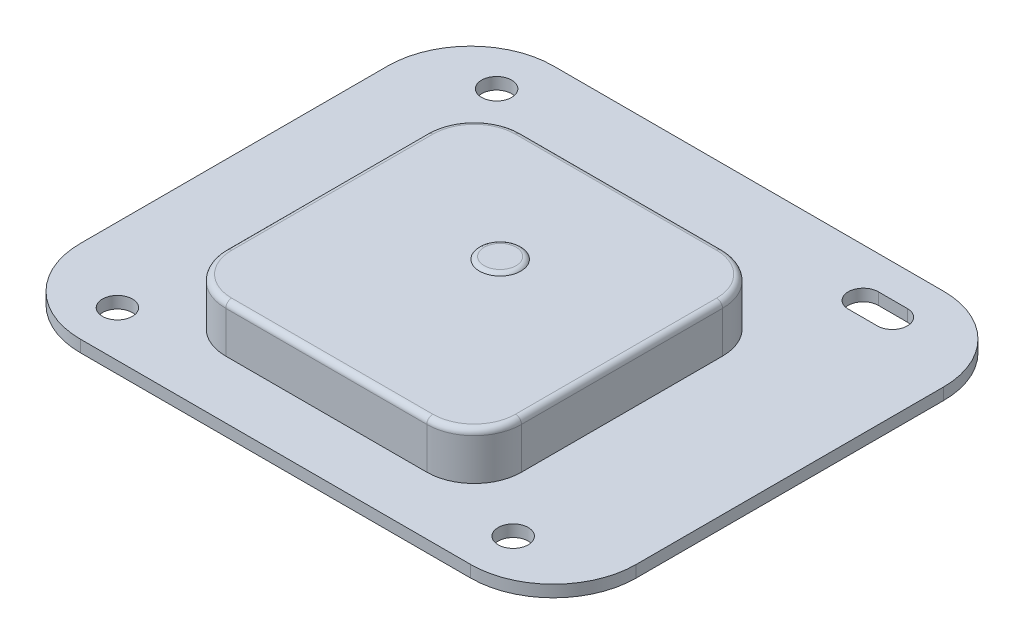
SolidWorks part; units mm, degrees
ref_plane "Front Plane" through (0, 0, 0) normal (0, 0, 1) x (1, 0, 0)
ref_plane "Top Plane" through (0, 0, 0) normal (0, 1, 0) x (1, 0, 0)
ref_plane "Right Plane" through (0, 0, 0) normal (1, 0, 0) x (0, 0, -1)
sketch "Sketch3" plane through (0, 0, 0) normal (0, 1, 0) x (1, 0, 0)
  line L0 (23.5, 20) -> (23.5, -20) construction
  line L1 (-23.5, -20) -> (23.5, -20) construction
  line L2 (-23.5, 20) -> (-23.5, -20) construction
  line L3 (-23.5, 20) -> (23.5, 20) construction
  line L4 (23.5, 20) -> (23.5, -20)
  line L5 (-23.5, -20) -> (23.5, -20)
  line L6 (-23.5, 20) -> (-23.5, -20)
  line L7 (-23.5, 20) -> (23.5, 20)
  line L8 (5.2, -11.1) -> (16.8, -11.1) construction
  line L9 (16.8, 3.9) -> (16.8, -11.1) construction
  line L10 (5.2, 3.9) -> (16.8, 3.9) construction
  line L11 (5.2, 3.9) -> (5.2, -11.1) construction
  line L12 (-20.5, 10) -> (-14.9, 10) construction
  line L13 (-20.5, 10) -> (-20.5, -0.9) construction
  line L14 (-20.5, -0.9) -> (-14.9, -0.9) construction
  line L15 (-14.9, 10) -> (-14.9, -0.9) construction
  line L16 (5.2, -11.1) -> (16.8, -11.1)
  line L17 (16.8, 3.9) -> (16.8, -11.1)
  line L18 (5.2, 3.9) -> (16.8, 3.9)
  line L19 (5.2, 3.9) -> (5.2, -11.1)
  line L20 (-20.5, 10) -> (-14.9, 10)
  line L21 (-20.5, 10) -> (-20.5, -0.9)
  line L22 (-20.5, -0.9) -> (-14.9, -0.9)
  line L23 (-14.9, 10) -> (-14.9, -0.9)
  circle A0 centre (-17.23, 15.93) radius 1.27 construction
  circle A1 centre (16.23, 15.93) radius 1.27 construction
  circle A2 centre (-17.23, -16.13) radius 1.27 construction
  circle A3 centre (16.23, -16.13) radius 1.27 construction
  circle A4 centre (-17.23, 15.93) radius 1.27
  circle A5 centre (16.23, 15.93) radius 1.27
  circle A6 centre (-17.23, -16.13) radius 1.27
  circle A7 centre (16.23, -16.13) radius 1.27
sketch "Sketch4" plane through (0, 0, 0) normal (0, 1, 0) x (1, 0, 0)
  line L0 (13.77, 14.66) -> (16.23, 14.66)
  line L1 (13.77, 17.2) -> (16.23, 17.2)
  line L4 (23.5, -20) -> (23.5, 20)
  line L5 (-23.5, -20) -> (23.5, -20)
  line L6 (-23.5, 20) -> (-23.5, -20)
  line L7 (23.5, 20) -> (-23.5, 20)
  line L8 (23.5, -20) -> (23.5, 20)
  line L9 (-23.5, -20) -> (23.5, -20)
  line L10 (-23.5, 20) -> (-23.5, -20)
  line L11 (23.5, 20) -> (-23.5, 20)
  arc A0 (13.77, 17.2) -> (13.77, 14.66) centre (13.77, 15.93) ccw
  circle A1 centre (16.23, -16.13) radius 1.27
  circle A2 centre (16.23, -16.13) radius 1.27
  circle A3 centre (-17.23, -16.13) radius 1.27
  circle A4 centre (-17.23, -16.13) radius 1.27
  circle A5 centre (16.23, 15.93) radius 1.27
  arc A6 (16.23, 14.66) -> (16.23, 17.2) centre (16.23, 15.93) ccw
  circle A7 centre (-17.23, 15.93) radius 1.27
  circle A8 centre (-17.23, 15.93) radius 1.27
  point P18 (12.5, 15.93)
  point P19 (17.5, 15.93)
  dimension "D6" = 5
  dimension "D1" = 0
  dimension "D2" = 0
  dimension "D3" = 0
  dimension "D4" = 0
  dimension "D5" = 0
extrude "Boss-Extrude1" add sketch "Sketch4" along normal blind 1
fillet "Fillet1" radius 7 4 edges at (-23.5, 0.5, -20) (23.5, 0.5, -20) (-23.5, 0.5, 20) (23.5, 0.5, 20)
sketch "Sketch5" plane through (0, 0, 0) normal (0, -1, 0) x (1, 0, 0)
  line L0 (5.2, -3.9) -> (5.2, 11.1) construction
  line L1 (5.2, 11.1) -> (16.8, 11.1) construction
  line L2 (5.2, -3.9) -> (16.8, -3.9) construction
  line L3 (16.8, -3.9) -> (16.8, 11.1) construction
  line L4 (5.2, -3.9) -> (5.2, 11.1)
  line L5 (5.2, 11.1) -> (16.8, 11.1)
  line L6 (5.2, -3.9) -> (16.8, -3.9)
  line L7 (16.8, -3.9) -> (16.8, 11.1)
extrude "Boss-Extrude2" add sketch "Sketch5" along normal blind 2.5
sketch "Sketch6" plane through (0, 0, 0) normal (0, -1, 0) x (1, 0, 0)
  line L0 (-20.5, -10) -> (-20.5, 0.9) construction
  line L1 (-20.5, 0.9) -> (-14.9, 0.9) construction
  line L2 (-20.5, -10) -> (-14.9, -10) construction
  line L3 (-14.9, -10) -> (-14.9, 0.9) construction
  line L4 (-20.5, -10) -> (-20.5, 0.9)
  line L5 (-20.5, 0.9) -> (-14.9, 0.9)
  line L6 (-20.5, -10) -> (-14.9, -10)
  line L7 (-14.9, -10) -> (-14.9, 0.9)
extrude "Boss-Extrude3" add sketch "Sketch6" along normal blind 4.5
sketch "Sketch7" plane through (0, 1, 0) normal (0, 1, 0) x (1, 0, 0)
  line L0 (23.5, -13) -> (23.5, 13) construction
  line L1 (-13.1, 9.9) -> (11.9, 9.9)
  line L2 (-13.1, 9.9) -> (-13.1, -15.1)
  line L3 (-13.1, -15.1) -> (11.9, -15.1)
  line L4 (11.9, 9.9) -> (11.9, -15.1)
  line L5 (16.5, 20) -> (-16.5, 20) construction
  dimension "D1" = 25
  dimension "D2" = 11.6
  dimension "D3" = 10.1
extrude "Boss-Extrude4" add sketch "Sketch7" along normal blind 4
fillet "Fillet2" radius 4 4 edges at (-13.1, 3, -9.9) (-13.1, 3, 15.1) (11.9, 3, 15.1) (11.9, 3, -9.9)
sketch "Sketch8" plane through (0, 5, 0) normal (0, 1, 0) x (1, 0, 0)
  line L0 (-0.6, 9.9) -> (-0.6, -15.1) construction
  line L4 (11.9, 9.9) -> (-13.1, 9.9)
  line L5 (11.9, -15.1) -> (11.9, 9.9)
  line L6 (-13.1, -15.1) -> (11.9, -15.1)
  line L7 (-13.1, 9.9) -> (-13.1, -15.1)
  line L8 (11.9, 9.9) -> (-13.1, 9.9) construction
  line L9 (11.9, -15.1) -> (11.9, 9.9) construction
  line L10 (-13.1, -15.1) -> (11.9, -15.1) construction
  line L11 (-13.1, 9.9) -> (-13.1, -15.1) construction
  circle A0 centre (-0.6, -0.4) radius 1.75
  point P8 (0, 0)
  dimension "D2" = 3.5
  dimension "D3" = 10.3
  dimension "D1" = 0
extrude "Boss-Extrude5" add sketch "Sketch8" along normal blind 0.2
fillet "Fillet3" radius 0.5 1 edges at (-0.6, 5.2, 2.15)
sketch "Sketch9" plane through (0, 0, 0) normal (0, -1, 0) x (1, 0, 0)
  line L0 (16.5, -20) -> (-16.5, -20) construction
  line L1 (-5, -15.2) -> (3, -15.2)
  line L2 (-5, -15.2) -> (-5, -20.7)
  line L3 (-5, -20.7) -> (3, -20.7)
  line L4 (3, -15.2) -> (3, -20.7)
  line L5 (-23.5, -13) -> (-23.5, 13) construction
  dimension "D1" = 0.7
  dimension "D2" = 8
  dimension "D3" = 5.5
  dimension "D4" = 18.5
extrude "Boss-Extrude6" add sketch "Sketch9" along normal blind 2.4
fillet "Fillet4" radius 0.5 8 edges at (10.7284, 5, 13.9284) (-0.6, 5, 15.1) (-11.9284, 5, 13.9284) (-13.1, 5, 2.6) (-11.9284, 5, -8.7284) (-0.6, 5, -9.9) (10.7284, 5, -8.7284) (11.9, 5, 2.6)
